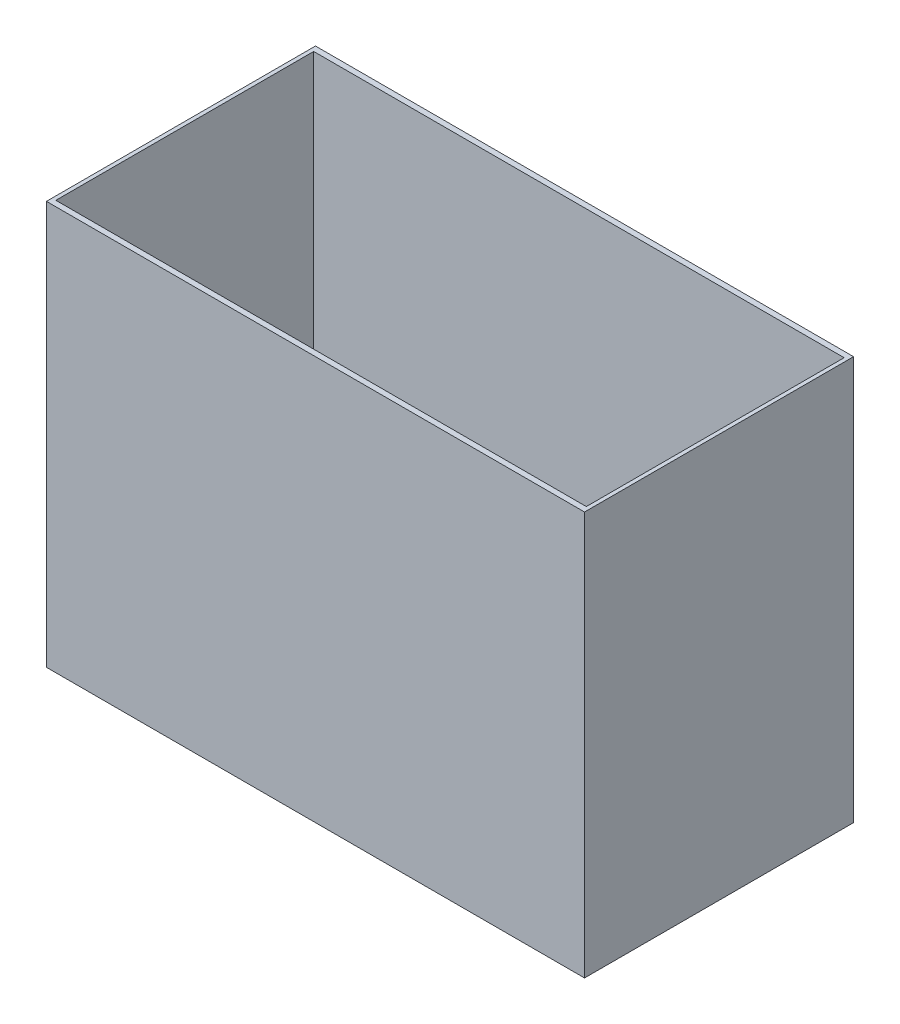
SolidWorks part; units mm, degrees
ref_plane "Front Plane" through (0, 0, 0) normal (0, 0, 1) x (1, 0, 0)
ref_plane "Top Plane" through (0, 0, 0) normal (0, 1, 0) x (1, 0, 0)
ref_plane "Right Plane" through (0, 0, 0) normal (1, 0, 0) x (0, 0, -1)
other "Bounding Box"
ref_plane "Default Plane" through (-292.1, 0, -139.7) normal (0, 1, 0) x (1, 0, 0)
sketch "Sketch1" plane through (0, 0, 0) normal (0, 1, 0) x (1, 0, 0)
  line L0 (-292.1, 0) -> (292.1, 0) construction
  line L1 (-292.1, 139.7) -> (292.1, 139.7)
  line L2 (-292.1, 139.7) -> (-292.1, -139.7)
  line L3 (-292.1, -139.7) -> (292.1, -139.7)
  line L4 (292.1, 139.7) -> (292.1, -139.7)
  line L5 (0, 139.7) -> (0, -139.7) construction
  point P8 (0, 0)
  dimension "D1" = 584.2
  dimension "D2" = 279.4
extrude "Boss-Extrude1" add sketch "Sketch1" along normal blind 12.7
sketch "Sketch2" plane through (0, 12.7, 0) normal (0, 1, 0) x (1, 0, 0)
  line L1 (-241.3, -107.95) -> (-152.4, -107.95)
  line L2 (-241.3, -107.95) -> (-241.3, -88.9)
  line L3 (-241.3, -88.9) -> (-152.4, -88.9)
  line L4 (-152.4, -107.95) -> (-152.4, -88.9)
  line L5 (-241.3, -107.95) -> (-152.4, -88.9) construction
  line L6 (-241.3, -88.9) -> (-152.4, -107.95) construction
  line L7 (-292.1, 139.7) -> (-292.1, -139.7) construction
  line L8 (-292.1, 0) -> (86.8038, 0) construction
  point P0 (-196.85, -98.425)
  dimension "D1" = 19.05
  dimension "D2" = 88.9
  dimension "D3" = 177.8
  dimension "D4" = 50.8
extrude "Boss-Extrude2" [suppressed] add sketch "Sketch2" along normal blind 304.8 separate body contours L2 L1 L4 L3
pattern_linear "LPattern1" [suppressed] count 2 spacing 304.8 of bodies 101
pattern_linear "LPattern2" [suppressed] count 2 spacing 215.9 of bodies 101
sketch "Sketch3" plane through (0, 0, 0) normal (0, 1, 0) x (1, 0, 0)
  line L1 (-304.8, -152.4) -> (304.8, -152.4)
  line L2 (-304.8, -152.4) -> (-304.8, 152.4)
  line L3 (-304.8, 152.4) -> (304.8, 152.4)
  line L4 (304.8, -152.4) -> (304.8, 152.4)
  line L5 (-304.8, -152.4) -> (304.8, 152.4) construction
  line L6 (-304.8, 152.4) -> (304.8, -152.4) construction
  line L7 (-300.482, -146.05) -> (300.482, -146.05)
  line L8 (-300.482, -146.05) -> (-300.482, 146.05)
  line L9 (-300.482, 146.05) -> (300.482, 146.05)
  line L10 (300.482, -146.05) -> (300.482, 146.05)
  line L11 (-300.482, -146.05) -> (300.482, 146.05) construction
  line L12 (-300.482, 146.05) -> (300.482, -146.05) construction
  point P0 (0, 0)
  point P6 (0, 0)
  dimension "D1" = 609.6
  dimension "D2" = 304.8
  dimension "D3" = 292.1
  dimension "D4" = 600.964
extrude "Boss-Extrude3" add sketch "Sketch3" along normal blind 457.2 separate body
